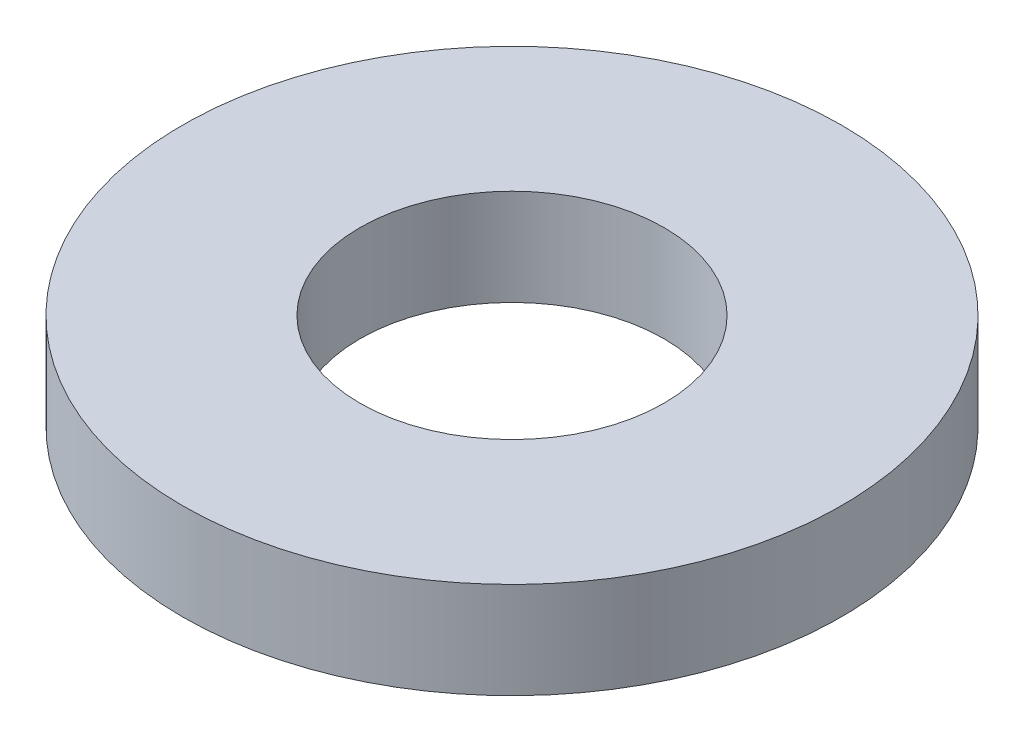
SolidWorks part; units mm, degrees
ref_plane "Front Plane" through (0, 0, 0) normal (0, 0, 1) x (1, 0, 0)
ref_plane "Top Plane" through (0, 0, 0) normal (0, 1, 0) x (1, 0, 0)
ref_plane "Right Plane" through (0, 0, 0) normal (1, 0, 0) x (0, 0, -1)
sketch "Sketch1" plane through (0, 0, 0) normal (0, 1, 0) x (1, 0, 0)
  circle A0 centre (0, 0) radius 65
  dimension "FLANGE_OD" = 130
extrude "Boss-Extrude1" add sketch "Sketch1" along normal blind 19
sketch "Sketch2" plane through (0, 0, 0) normal (0, 1, 0) x (1, 0, 0)
  circle A0 centre (0, 0) radius 30
  dimension "BORE_D" = 60
extrude "Cut-Extrude1" cut sketch "Sketch2" along normal through all
sketch "Sketch3" plane through (0, 19, 0) normal (0, 1, 0) x (1, 0, 0)
  circle A0 centre (0, 0) radius 20.7485 construction
  circle A1 centre (-20.7485, 0) radius 5.5654
  dimension "BOLT_D" = 11.1308
  dimension "BOLT_PCD" = 41.4969
extrude "Cut-Extrude2" cut sketch "Sketch3" against normal blind 16.8518 rebuild error yes
pattern_circular "CirPattern1" count 3 over 360 rebuild error yes
